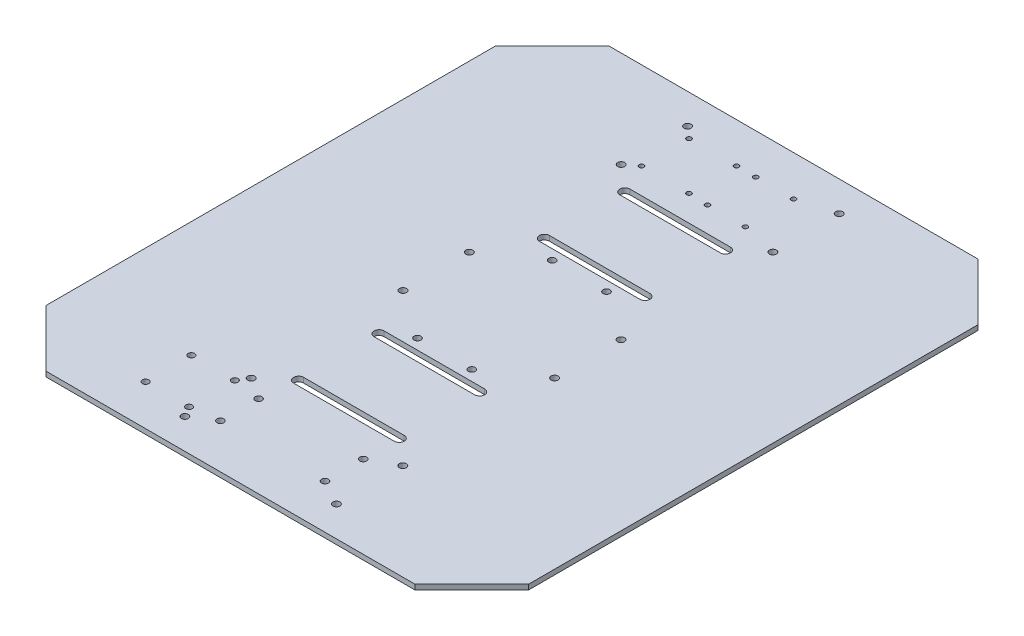
SolidWorks part; units mm, degrees
ref_plane "Front Plane" through (0, 0, 0) normal (0, 0, 1) x (1, 0, 0)
ref_plane "Top Plane" through (0, 0, 0) normal (0, 1, 0) x (1, 0, 0)
ref_plane "Right Plane" through (0, 0, 0) normal (1, 0, 0) x (0, 0, -1)
sketch "Sketch1" plane through (0, 0, 0) normal (0, 1, 0) x (1, 0, 0)
  line L0 (-121.2861, 87.138) -> (-85.365, 123.059)
  line L1 (-121.2861, 123.059) -> (183.5139, 123.059)
  line L2 (-121.2861, 123.059) -> (-121.2861, -232.541)
  line L3 (-121.2861, -232.541) -> (183.5139, -232.541)
  line L4 (183.5139, 123.059) -> (183.5139, -232.541)
  line L5 (31.1139, 95.069) -> (31.1139, -294.9418) construction
  line L6 (-146.0448, -54.741) -> (218.038, -54.741) construction
  line L7 (183.5139, 87.138) -> (147.5929, 123.059)
  line L8 (183.5139, -196.62) -> (147.5929, -232.541)
  line L9 (-121.2861, -196.62) -> (-85.365, -232.541)
  circle A0 centre (-16.7651, 104.009) radius 2.2225
  circle A1 centre (78.9929, 104.009) radius 2.2225
  circle A2 centre (-16.7651, 62.099) radius 2.2225
  circle A3 centre (78.9929, 62.099) radius 2.2225
  circle A4 centre (-16.7651, -171.581) radius 2.2225
  circle A5 centre (78.9929, -171.581) radius 2.2225
  circle A6 centre (78.9929, -213.491) radius 2.2225
  circle A7 centre (-16.7651, -213.491) radius 2.2225
  circle A8 centre (-16.7651, -33.786) radius 2.2225
  circle A9 centre (78.9929, -33.786) radius 2.2225
  circle A10 centre (78.9929, -75.696) radius 2.2225
  circle A11 centre (-16.7651, -75.696) radius 2.2225
  point P8 (31.1139, 123.059)
  point P11 (-121.2861, -54.741)
  dimension "D6" = 95.758
  dimension "D13" = 4.445
  dimension "D1" = 304.8
  dimension "D2" = 355.6
  dimension "D3" = 45
  dimension "D4" = 50.8
  dimension "D5" = 41.91
  dimension "D7" = 104.521
  dimension "D8" = 19.05
  dimension "D9" = 41.91
  dimension "D10" = 20.955
  dimension "D11" = 95.758
  dimension "D12" = 47.879
extrude "Boss-Extrude1" add sketch "Sketch1" along normal blind 3.175 contours L2 L9 L3 L8 L4 L7 L1 L0 region at (31.1139, 0, 54.741)
sketch "Sketch2" plane through (0, 3.175, 0) normal (0, 1, 0) x (1, 0, 0)
  line L0 (31.1139, 123.059) -> (31.1139, -287.8465) construction
  line L1 (-85.365, 123.059) -> (147.5929, 123.059) construction
  line L2 (183.5139, -54.741) -> (-158.2106, -54.741) construction
  line L3 (183.5139, 87.138) -> (183.5139, -196.62) construction
  circle A0 centre (13.8419, -12.069) radius 2.159
  circle A1 centre (48.1319, -12.069) radius 2.159
  circle A2 centre (13.8419, -97.159) radius 2.159
  circle A3 centre (48.1319, -97.159) radius 2.159
  dimension "D5" = 4.318
  dimension "D6" = 4.318
  dimension "D7" = 4.318
  dimension "D8" = 4.318
  dimension "D1" = 17.272
  dimension "D2" = 34.29
  dimension "D3" = 85.09
  dimension "D4" = 42.672
extrude "Cut-Extrude1" cut sketch "Sketch2" against normal through all
sketch "Sketch4" plane through (0, 3.175, 0) normal (0, 1, 0) x (1, 0, 0)
  line L0 (-0.6361, 48.256) -> (62.8639, 48.256) construction
  line L1 (-0.6361, 51.431) -> (62.8639, 51.431)
  line L2 (-0.6361, 45.081) -> (62.8639, 45.081)
  line L3 (-0.6361, -2.544) -> (62.8639, -2.544) construction
  line L4 (-0.6361, 0.631) -> (62.8639, 0.631)
  line L5 (-0.6361, -5.719) -> (62.8639, -5.719)
  line L6 (31.1139, 123.059) -> (31.1139, -75.2432) construction
  line L7 (-85.365, 123.059) -> (147.5929, 123.059) construction
  line L8 (-121.2861, -54.741) -> (257.7387, -54.741) construction
  line L9 (-121.2861, 87.138) -> (-121.2861, -196.62) construction
  line L10 (31.1139, -232.541) -> (31.1139, -34.2388) construction
  line L11 (-0.6361, -106.938) -> (62.8639, -106.938) construction
  line L12 (-0.6361, -110.113) -> (62.8639, -110.113)
  line L13 (-0.6361, -103.763) -> (62.8639, -103.763)
  line L14 (-0.6361, -157.738) -> (62.8639, -157.738) construction
  line L15 (-0.6361, -160.913) -> (62.8639, -160.913)
  line L16 (-0.6361, -154.563) -> (62.8639, -154.563)
  arc A0 (-0.6361, 51.431) -> (-0.6361, 45.081) centre (-0.6361, 48.256) ccw
  arc A1 (62.8639, 45.081) -> (62.8639, 51.431) centre (62.8639, 48.256) ccw
  arc A2 (-0.6361, 0.631) -> (-0.6361, -5.719) centre (-0.6361, -2.544) ccw
  arc A3 (62.8639, -5.719) -> (62.8639, 0.631) centre (62.8639, -2.544) ccw
  circle A4 centre (48.1319, -12.069) radius 2.159 construction
  arc A5 (-0.6361, -110.113) -> (-0.6361, -103.763) centre (-0.6361, -106.938) cw
  arc A6 (62.8639, -103.763) -> (62.8639, -110.113) centre (62.8639, -106.938) cw
  arc A7 (-0.6361, -160.913) -> (-0.6361, -154.563) centre (-0.6361, -157.738) cw
  arc A8 (62.8639, -154.563) -> (62.8639, -160.913) centre (62.8639, -157.738) cw
  point P2 (31.1139, 48.256)
  point P7 (31.1139, -2.544)
  point P28 (31.1139, -106.938)
  point P35 (31.1139, -157.738)
  dimension "D1" = 63.5
  dimension "D2" = 63.5
  dimension "D3" = 6.35
  dimension "D4" = 6.35
  dimension "D5" = 44.45
  dimension "D6" = 6.35
extrude "Cut-Extrude2" cut sketch "Sketch4" against normal through all
sketch "Sketch7" plane through (0, 3.175, 0) normal (0, 1, 0) x (1, 0, 0)
  line L1 (-121.2861, 87.138) -> (-121.2861, -196.62) construction
  line L3 (-85.365, 123.059) -> (147.5929, 123.059) construction
  circle A0 centre (-9.5261, 67.687) radius 1.524
  circle A1 centre (20.4459, 67.687) radius 1.524
  circle A2 centre (-9.5261, 97.659) radius 1.524
  circle A3 centre (20.4459, 97.659) radius 1.524
  point P4 (0, 0)
  point P9 (-1.859, -176.8776)
  point P10 (-5.9387, -176.5335)
  point P11 (0, 0)
  point P12 (0, 0)
  point P16 (0, 0)
  dimension "D1" = 3.048
  dimension "D2" = 3.048
  dimension "D3" = 29.972
  dimension "D4" = 29.972
  dimension "D5" = 25.4
  dimension "D6" = 111.76
extrude "Cut-Extrude3" cut sketch "Sketch7" against normal through all
sketch "Sketch8" plane through (0, 3.175, 0) normal (0, 1, 0) x (1, 0, 0)
  line L1 (183.5139, 87.138) -> (183.5139, -196.62) construction
  line L2 (-85.365, 123.059) -> (147.5929, 123.059) construction
  circle A0 centre (32.6379, 67.179) radius 1.524
  circle A1 centre (32.6379, 97.659) radius 1.524
  circle A2 centre (56.5139, 67.179) radius 1.524
  circle A3 centre (56.5139, 97.659) radius 1.524
  point P4 (0, 0)
  point P5 (0, 0)
  point P10 (56.7326, -209.7366)
  point P11 (58.2355, -178.0893)
  point P12 (51.5368, -207.1523)
  point P13 (51.365, -176.6723)
  point P14 (0, 0)
  point P15 (0, 0)
  point P16 (0, 0)
  dimension "D1" = 3.048
  dimension "D2" = 30.48
  dimension "D3" = 23.876
  dimension "D4" = 25.4
  dimension "D5" = 127
extrude "Cut-Extrude4" cut sketch "Sketch8" against normal through all and the other way through all
sketch "Sketch9" plane through (0, 0, 0) normal (0, -1, 0) x (-1, 0, 0)
  line L0 (85.365, -232.541) -> (-147.5929, -232.541) construction
  line L1 (121.2861, 87.138) -> (121.2861, -196.62) construction
  circle A0 centre (48.1341, -206.887) radius 2.032
  circle A1 centre (20.7021, -206.887) radius 2.032
  circle A2 centre (48.1341, -177.931) radius 2.032
  circle A3 centre (20.7021, -177.931) radius 2.032
  point P8 (0, 0)
  point P9 (0, 0)
  dimension "D1" = 4.064
  dimension "D2" = 27.432
  dimension "D3" = 28.956
  dimension "D4" = 25.654
  dimension "D5" = 73.152
extrude "Cut-Extrude5" cut sketch "Sketch9" against normal through all
sketch "Sketch10" plane through (0, 0, 0) normal (0, -1, 0) x (1, 0, 0)
  line L0 (-85.365, 232.541) -> (147.5929, 232.541) construction
  line L1 (183.5139, -87.138) -> (183.5139, 196.62) construction
  circle A0 centre (-3.1761, 204.601) radius 2.159
  circle A1 centre (62.8639, 204.601) radius 2.159
  circle A2 centre (-3.1761, 180.471) radius 2.159
  circle A3 centre (62.8639, 180.471) radius 2.159
  point P4 (0, 0)
  point P9 (-5.2207, 175.8971)
  point P10 (60.1093, 173.3263)
  point P11 (-5.9307, 173.4487)
  point P12 (0, 0)
  point P13 (0, 0)
  dimension "D1" = 4.318
  dimension "D2" = 66.04
  dimension "D4" = 27.94
  dimension "D6" = 4.318
  dimension "D7" = 4.318
  dimension "D8" = 4.318
  dimension "D3" = 24.13
  dimension "D5" = 120.65
extrude "Cut-Extrude6" cut sketch "Sketch10" against normal through all
